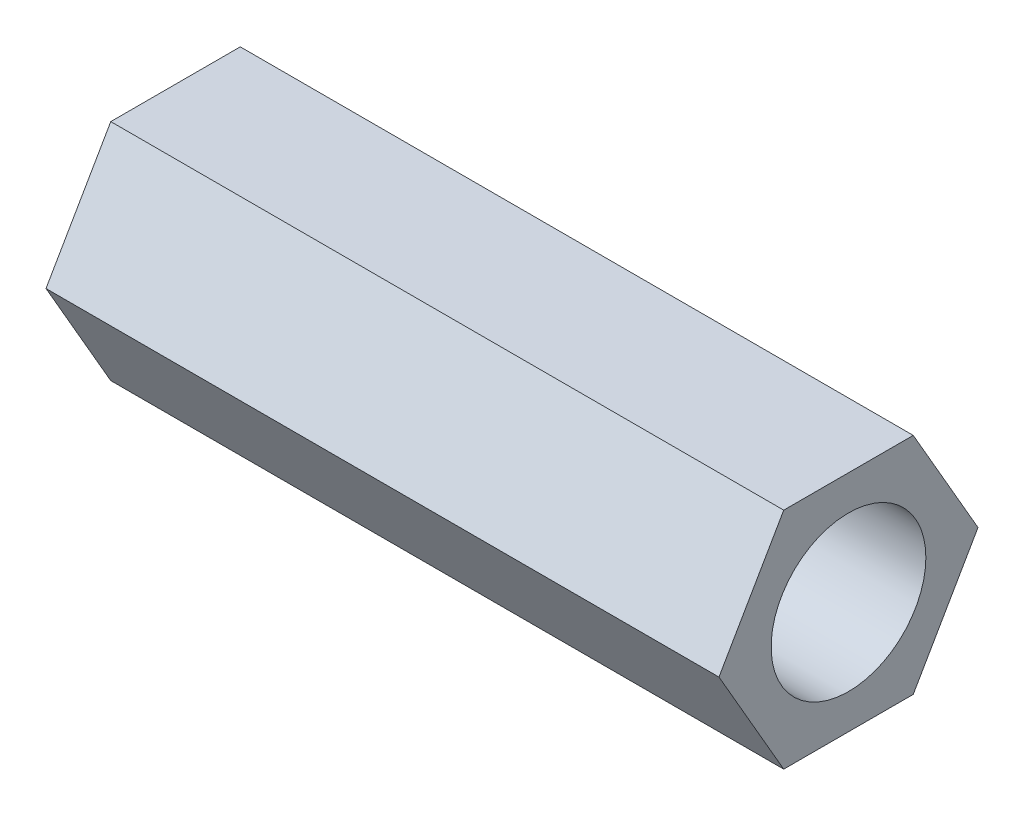
SolidWorks part; units mm, degrees
ref_plane "Front" through (0, 0, 0) normal (0, 0, 1) x (1, 0, 0)
ref_plane "Top" through (0, 0, 0) normal (0, 1, 0) x (1, 0, 0)
ref_plane "Right" through (0, 0, 0) normal (1, 0, 0) x (0, 0, -1)
sketch "Sketch1" plane through (0, 0, 0) normal (1, 0, 0) x (0, 0, -1)
  line L1 (7.3323, 0) -> (3.6662, 6.35)
  line L2 (3.6662, 6.35) -> (-3.6662, 6.35)
  line L3 (-3.6662, 6.35) -> (-7.3323, 0)
  line L4 (-7.3323, 0) -> (-3.6662, -6.35)
  line L5 (-3.6662, -6.35) -> (3.6662, -6.35)
  line L6 (3.6662, -6.35) -> (7.3323, 0)
  circle A0 centre (0, 0) radius 6.35 construction
  dimension "D1" = 12.7
extrude "Boss-Extrude1" add sketch "Sketch1" along normal blind 38.1
sketch "Sketch2" plane through (38.1, 0, 0) normal (1, 0, 0) x (0, 0, -1)
  circle A0 centre (0, 0) radius 4.381
  dimension "D1" = 8.762
extrude "Cut-Extrude1" cut sketch "Sketch2" against normal through all
